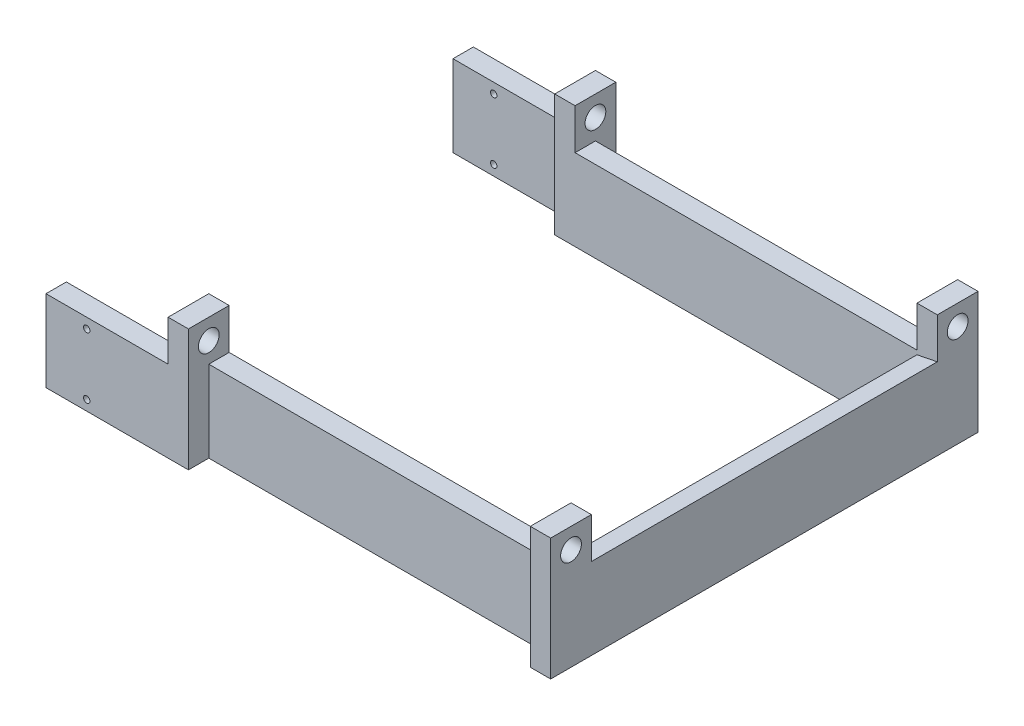
SolidWorks part; units mm, degrees
ref_plane "Front Plane" through (0, 0, 0) normal (0, 0, 1) x (1, 0, 0)
ref_plane "Top Plane" through (0, 0, 0) normal (0, 1, 0) x (1, 0, 0)
ref_plane "Right Plane" through (0, 0, 0) normal (1, 0, 0) x (0, 0, -1)
sketch "Sketch1" plane through (0, 0, 0) normal (0, 1, 0) x (1, 0, 0)
  line L0 (3.175, 114.3) -> (0, 114.3)
  line L1 (0, 0) -> (119.38, 0)
  line L2 (0, 0) -> (0, 6.35)
  line L3 (0, 120.65) -> (119.38, 120.65)
  line L4 (119.38, 0) -> (119.38, 120.65)
  line L5 (3.175, 114.3) -> (113.03, 114.3)
  line L7 (3.175, 6.35) -> (113.03, 6.35)
  line L8 (113.03, 114.3) -> (113.03, 6.35)
  line L9 (3.175, 6.35) -> (0, 6.35)
  line L10 (0, 114.3) -> (0, 120.65)
  dimension "D1" = 120.65
  dimension "D2" = 113.03
  dimension "D3" = 6.35
  dimension "D5" = 6.35
  dimension "D6" = 107.95
extrude "Boss-Extrude1" add sketch "Sketch1" along normal blind 25.4
sketch "Sketch2" plane through (0, 0, 0) normal (0, 0, 1) x (1, 0, 0)
  line L0 (119.38, 25.4) -> (113.03, 24.13)
  line L1 (113.03, 24.13) -> (113.03, 25.4)
  line L2 (0, 25.4) -> (119.38, 25.4) construction
  line L4 (113.03, 25.4) -> (119.38, 25.4)
  dimension "D2" = 1.27
extrude "Cut-Extrude1" cut sketch "Sketch2" against normal up to surface (114.3 mm away) from surface up to face at (56.515, 12.7, -114.3) starting at face at (56.515, 12.7, -6.35)
sketch "Sketch3" plane through (0, 0, 0) normal (0, 0, 1) x (1, 0, 0)
  line L0 (0, 25.4) -> (119.38, 25.4) construction
  line L1 (6.35, 25.4) -> (-38.1, 25.4)
  line L2 (6.35, 25.4) -> (6.35, 0)
  line L3 (6.35, 0) -> (-38.1, 0)
  line L4 (-38.1, 25.4) -> (-38.1, 0)
  line L5 (0, 25.4) -> (0, 0) construction
  dimension "D1" = 6.35
  dimension "D2" = 38.1
extrude "Boss-Extrude2" add sketch "Sketch3" along normal blind 6.35
extrude "Boss-Extrude3" add sketch "Sketch3<2>" against normal blind 6.35 from surface starting at face at (59.69, 12.7, -120.65)
sketch "Sketch3<2>" plane through (0, 0, 0) normal (0, 0, 1) x (1, 0, 0) same geometry as "Sketch3"
sketch "Sketch8" plane through (0, 25.4, 0) normal (0, 1, 0) x (1, 0, 0)
  line L0 (119.38, 60.325) -> (-5.0576, 60.325) construction
  line L1 (119.38, -6.35) -> (113.03, -6.35)
  line L2 (119.38, -6.35) -> (119.38, 6.35)
  line L4 (113.03, -6.35) -> (113.03, 6.35)
  line L5 (113.03, 6.35) -> (119.38, 6.35)
  line L6 (59.69, 114.3) -> (59.69, -20.9935) construction
  line L7 (0, 114.3) -> (119.38, 114.3) construction
  line L8 (119.38, 114.3) -> (119.38, 6.35) construction
  line L9 (6.35, -6.35) -> (6.35, 6.35)
  line L10 (0, 6.35) -> (6.35, 6.35)
  line L11 (0, -6.35) -> (0, 6.35)
  line L12 (0, -6.35) -> (6.35, -6.35)
  line L22 (0, 127) -> (6.35, 127)
  line L23 (0, 127) -> (0, 114.3)
  line L24 (0, 114.3) -> (6.35, 114.3)
  line L25 (6.35, 127) -> (6.35, 114.3)
  line L26 (113.03, 127) -> (113.03, 114.3)
  line L27 (119.38, 114.3) -> (113.03, 114.3)
  line L28 (119.38, 127) -> (119.38, 114.3)
  line L29 (119.38, 127) -> (113.03, 127)
  dimension "D1" = 12.7
extrude "Boss-Extrude4" add sketch "Sketch8" along normal blind 38.1 from surface starting at face at (21.1138, 0, -60.325)
sketch "Sketch9" plane through (119.38, 0, 0) normal (1, 0, 0) x (0, 0, -1)
  line L0 (-6.35, 38.1) -> (6.35, 38.1) construction
  line L3 (60.325, 36.7762) -> (60.325, 19.9574) construction
  line L4 (6.35, 38.1) -> (6.35, 0) construction
  line L5 (-6.35, 38.1) -> (-6.35, 0) construction
  circle A0 centre (0, 31.75) radius 3.2385
  circle A1 centre (120.65, 31.75) radius 3.2385
  dimension "D1" = 6.477
  dimension "D4" = 53.975
  dimension "D2" = 6.35
  dimension "D3" = 6.35
extrude "Cut-Extrude2" cut sketch "Sketch9" against normal through all both and the other way through all
sketch "Sketch10" plane through (0, 0, 6.35) normal (0, 0, 1) x (1, 0, 0)
  line L0 (0, 25.4) -> (-38.1, 25.4) construction
  line L1 (-38.1, 25.4) -> (-38.1, 0) construction
  circle A0 centre (-25.4, 22.225) radius 1
  circle A1 centre (-25.4, 3.175) radius 1
  dimension "D2" = 2
  dimension "D4" = 2
  dimension "D1" = 3.175
  dimension "D3" = 12.7
  dimension "D5" = 19.05
  dimension "D6" = 12.7
extrude "Cut-Extrude3" cut sketch "Sketch10" against normal through all
equation "\"tightTol\" = 0.005in"
equation "\"normTol\"= 0.01in"
equation "\"looseTol\"= 0.02in"
equation "\"D1@Sketch9\"=\"tightTol\"+0.250000in"
equation "\"D2@Sketch10\"=2mm"
equation "\"D4@Sketch10\"=2mm"
